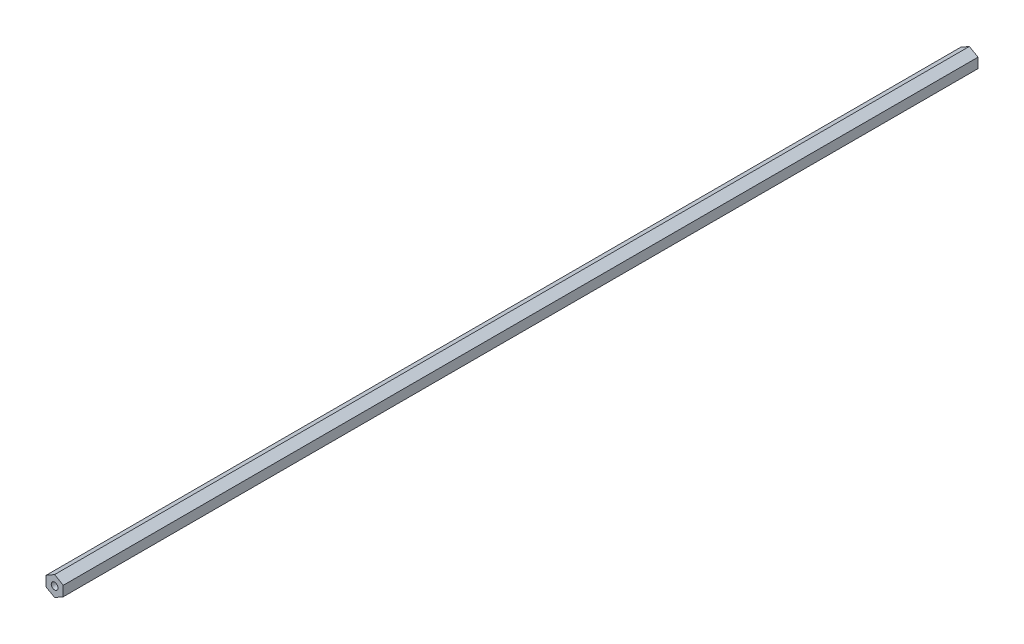
SolidWorks part; units mm, degrees
ref_plane "Front Plane" through (0, 0, 0) normal (0, 0, 1) x (1, 0, 0)
ref_plane "Top Plane" through (0, 0, 0) normal (0, 1, 0) x (1, 0, 0)
ref_plane "Right Plane" through (0, 0, 0) normal (1, 0, 0) x (0, 0, -1)
sketch "Sketch1" plane through (0, 0, 0) normal (0, 0, 1) x (1, 0, 0)
  line L1 (6.35, -3.6662) -> (6.35, 3.6662)
  line L2 (6.35, 3.6662) -> (0, 7.3323)
  line L3 (0, 7.3323) -> (-6.35, 3.6662)
  line L4 (-6.35, 3.6662) -> (-6.35, -3.6662)
  line L5 (-6.35, -3.6662) -> (0, -7.3323)
  line L6 (0, -7.3323) -> (6.35, -3.6662)
  circle A0 centre (0, 0) radius 6.35 construction
  point P1 (3.621, 6.35)
  point P10 (-7.3323, 0)
  point P11 (0, 0)
  dimension "D1" = 12.7
extrude "Boss-Extrude1" add sketch "Sketch1" along normal mid plane 673.6052
sketch "Sketch2" plane through (0, 0, 336.8026) normal (0, 0, 1) x (1, 0, 0)
  circle A0 centre (0, 0) radius 2.4892
  dimension "D1" = 4.9784
extrude "Cut-Extrude1" cut sketch "Sketch2" against normal blind 19.05
mirror "Mirror1" about plane through (0, 0, 0) normal (0, 0, 1) of "Cut-Extrude1"
